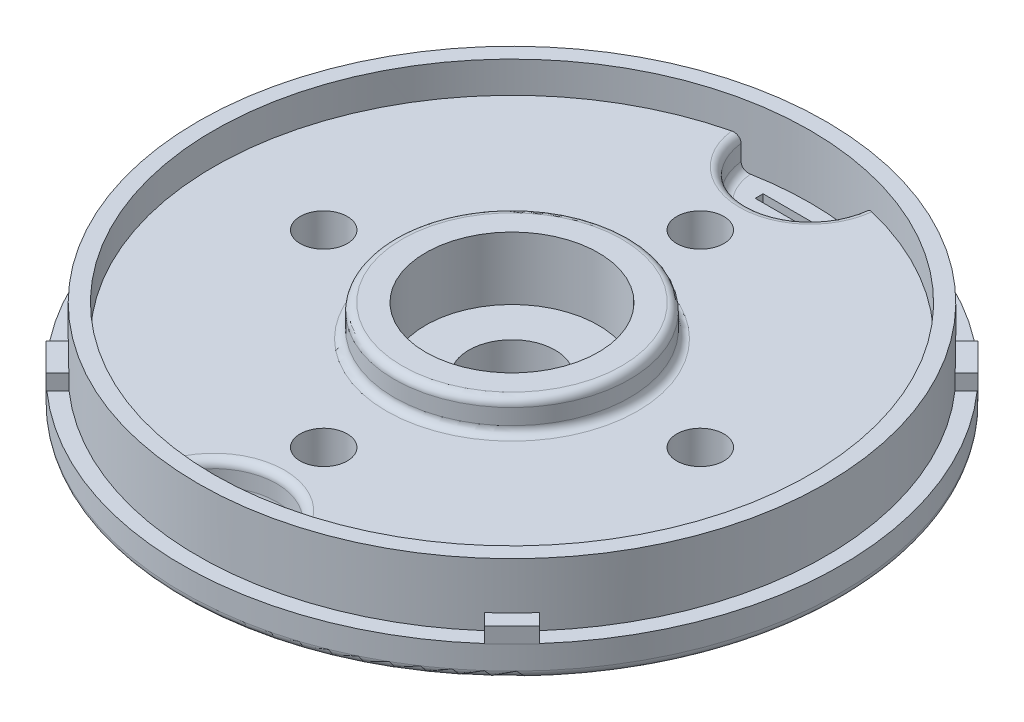
SolidWorks part; units mm, degrees
ref_plane "Front Plane" through (0, 0, 0) normal (0, 0, 1) x (1, 0, 0)
ref_plane "Top Plane" through (0, 0, 0) normal (0, 1, 0) x (1, 0, 0)
ref_plane "Right Plane" through (0, 0, 0) normal (1, 0, 0) x (0, 0, -1)
sketch "Sketch1" plane through (0, 0, 0) normal (0, 1, 0) x (1, 0, 0)
  circle A0 centre (0, 0) radius 20
  dimension "D1" = 40
extrude "Boss-Extrude1" add sketch "Sketch1" along normal blind 4
sketch "Sketch2" plane through (0, 4, 0) normal (0, 1, 0) x (1, 0, 0)
  circle A0 centre (0, 0) radius 19
  circle A1 centre (0, 0) radius 7.5
  circle A2 centre (0, 0) radius 20 construction
  dimension "D1" = 15
  dimension "D2" = 1
extrude "Cut-Extrude1" cut sketch "Sketch2" against normal blind 2
fillet "Fillet3" radius 0.5 2 edges at (0, 2, 7.5) (0, 4, 7.5)
sketch "Sketch3" plane through (0, 4, 0) normal (0, 1, 0) x (1, 0, 0)
  circle A0 centre (0, 0) radius 5.5
  dimension "D1" = 11
sketch "Sketch6" plane through (0, 0, 0) normal (0, -1, 0) x (1, 0, 0)
  circle A0 centre (0, 0) radius 21
  dimension "D1" = 42
extrude "Boss-Extrude4" add sketch "Sketch6" along normal blind 2
fillet "Fillet4" radius 0.5 1 edges at (0, -2, -21)
extrude "Cut-Extrude4" cut sketch "Sketch3" against normal blind 4
sketch "Sketch7" plane through (0, -2, 0) normal (0, -1, 0) x (1, 0, 0)
  circle A0 centre (0, 0) radius 2.75
  dimension "D1" = 5.5
extrude "Cut-Extrude5" cut sketch "Sketch7" against normal up to surface (6 mm away) up to face at (0, 4, 19)
sketch "Sketch8" plane through (0, 0, 0) normal (0, 1, 0) x (1, 0, 0)
  line L0 (-15.7331, 13.9654) -> (-14.9984, 13.2306)
  line L1 (-15.7331, 13.9654) -> (-13.9654, 15.7331)
  line L2 (-14.9984, 13.2306) -> (-13.2306, 14.9984)
  line L3 (-13.9654, 15.7331) -> (-13.2306, 14.9984)
  line L4 (-15.7331, 13.9654) -> (-13.2306, 14.9984) construction
  line L5 (-14.9984, 13.2306) -> (-13.9654, 15.7331) construction
  line L6 (0, 0) -> (-14.8492, 14.8492) construction
  line L7 (0, 0) -> (0, 21) construction
  circle A0 centre (0, 0) radius 20 construction
  circle A1 centre (0, 0) radius 21 construction
  point P1 (-14.4819, 14.4819)
  point P3 (-14.1145, 14.1145)
  dimension "D1" = 45
  dimension "D2" = 2.5
extrude "Boss-Extrude5" add sketch "Sketch8" along normal blind 1 contours L3 L2 L0 L1
pattern_circular "CirPattern1" count 4 over 360 about axis through (0, 4, 0) along (0, -1, 0) of "Boss-Extrude5"
sketch "Sketch9" plane through (0, -2, 0) normal (0, -1, 0) x (1, 0, 0)
  line L0 (0, 0) -> (0, 21) construction
  line L2 (-2, 18) -> (2, 18)
  line L3 (-2, 18) -> (-2, 17.5)
  line L4 (-2, 17.5) -> (2, 17.5)
  line L5 (2, 18) -> (2, 17.5)
  circle A0 centre (0, 0) radius 21 construction
  point P10 (0, 17.5)
  dimension "D1" = 4
  dimension "D2" = 0.5
  dimension "D3" = 18
extrude "TerminalSlot" cut sketch "Sketch9" against normal up to surface (4 mm away) up to face at (0, 2, 8)
pattern_circular "CirPattern2" count 2 over 360 about axis through (0, 4, 0) along (0, -1, 0) of "TerminalSlot"
sketch "Sketch10" plane through (0, 2, 0) normal (0, 1, 0) x (1, 0, 0)
  line L0 (-2, 18) -> (2, 18) construction
  arc A0 (-3.9778, 18.5789) -> (3.9778, 18.5789) centre (0, 19) ccw
  circle A1 centre (0, 0) radius 19 construction
  circle A2 centre (0, 0) radius 19 construction
  arc A3 (-3.9778, 18.5789) -> (3.9778, 18.5789) centre (0, 0) cw
  point P7 (0, 18)
  dimension "D1" = 4
extrude "Cut-Extrude7" cut sketch "Sketch10" against normal blind 2 contours A0 A3
pattern_circular "CirPattern3" count 2 over 360 about axis through (0, 2, 0) along (0, 1, 0) of "Cut-Extrude7"
fillet "Fillet2" radius 0.5 4 edges at (0, 0, 15) (0, 2, 15) (0, 0, -15) (0, 2, -15)
sketch "Sketch11" plane through (0, 2, 0) normal (0, 1, 0) x (1, 0, 0)
  line L0 (-12.7279, 12.7279) -> (-6.364, 6.364) construction
  line L1 (0, 0) -> (0, 21) construction
  line L2 (0, 0) -> (-6.364, 6.364) construction
  line L3 (-5.5068, 15.9186) -> (-4.0325, 8.8581)
  line L4 (-15.9186, 5.5068) -> (-8.8581, 4.0325)
  circle A0 centre (0, 0) radius 12.5 construction
  arc A1 (-16.6385, 6.8672) -> (-6.8672, 16.6385) centre (0, 0) cw
  arc A2 (-7.7883, 4.5103) -> (-4.5103, 7.7883) centre (0, 0) cw
  arc A3 (13.939, 15.7068) -> (-13.939, 15.7068) centre (0, 0) ccw construction
  arc A4 (-6.8672, 16.6385) -> (-5.5068, 15.9186) centre (-6.4857, 15.7142) cw
  arc A5 (-4.5103, 7.7883) -> (-4.0325, 8.8581) centre (-5.0114, 8.6537) ccw
  arc A6 (-7.7883, 4.5103) -> (-8.8581, 4.0325) centre (-8.6537, 5.0114) cw
  arc A7 (-16.6385, 6.8672) -> (-15.9186, 5.5068) centre (-15.7142, 6.4857) ccw
  point P15 (-5.7449, 17.0586)
  point P18 (-3.8787, 8.1213)
  point P21 (-8.1213, 3.8787)
  point P24 (-17.0586, 5.7449)
  dimension "D1" = 25
  dimension "D2" = 18
  dimension "D3" = 45
  dimension "D7" = 1
  dimension "D4" = 16
  dimension "D5" = 6
  dimension "D6" = 9
extrude "Cut-Extrude8" cut sketch "Sketch11" along normal blind 2 from surface contours A1 A4 L3 A5 A2 A6 L4 A7 starting at face at (0, -2, -17.75)
fillet "Fillet1" radius 0.5 16 edges at (-16.598, 0, -6.018) (-12.3883, 0, -4.7697) (-8.2459, 0, -4.0983) (-6.364, 0, -6.364) (-4.0983, 0, -8.2459) (-4.7697, 0, -12.3883) (-6.018, 0, -16.598) (-12.7279, 0, -12.7279) (-12.7279, -2, -12.7279) (-16.598, -2, -6.018) (-12.3883, -2, -4.7697) (-8.2459, -2, -4.0983) (-6.364, -2, -6.364) (-4.0983, -2, -8.2459) (-4.7697, -2, -12.3883) (-6.018, -2, -16.598)
pattern_circular "CirPattern5" count 4 over 360 about axis through (0, 2, 0) along (0, 1, 0) of "Cut-Extrude8", "Fillet1"
sketch "Sketch12" plane through (0, 2, 0) normal (0, 1, 0) x (1, 0, 0)
  circle A0 centre (0, 12) radius 1.5
  dimension "D2" = 3
  dimension "D1" = 12
extrude "Cut-Extrude9" cut sketch "Sketch12" against normal up to surface (4 mm away) up to face at (8.7963, -2, -8.7963)
pattern_circular "CirPattern6" count 4 over 360 about axis through (0, 2, 0) along (0, 1, 0) of "Cut-Extrude9"
